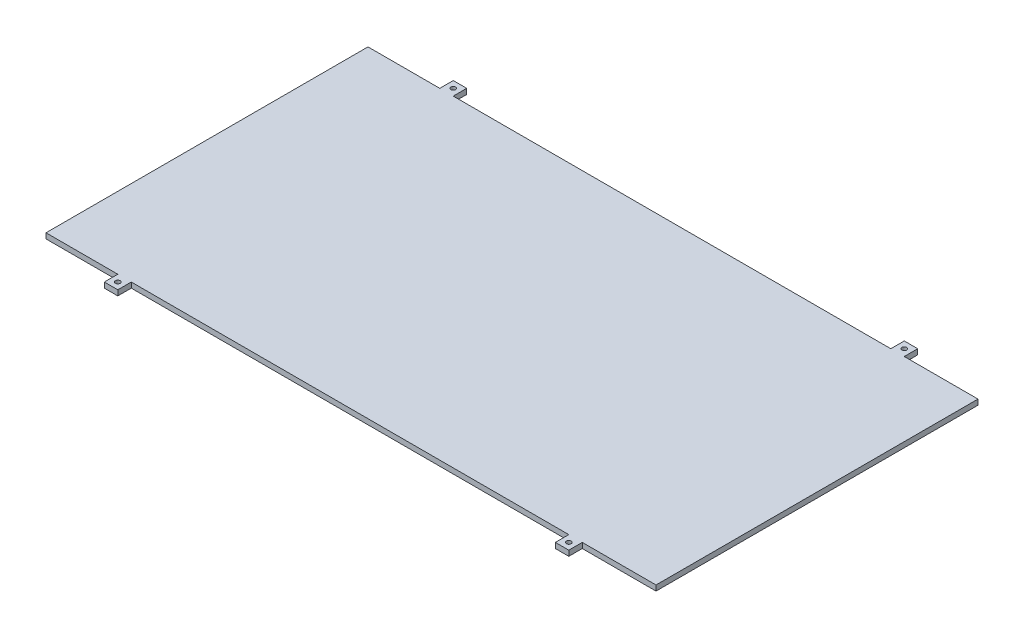
SolidWorks part; units mm, degrees
material "5052-H34"
ref_plane "Front Plane" through (0, 0, 0) normal (0, 0, 1) x (1, 0, 0)
ref_plane "Top Plane" through (0, 0, 0) normal (0, 1, 0) x (1, 0, 0)
ref_plane "Right Plane" through (0, 0, 0) normal (1, 0, 0) x (0, 0, -1)
sketch "Sketch1" plane through (0, 0, 0) normal (0, 0, 1) x (1, 0, 0)
  line L0 (-580.595, 4.4417) -> (-36.865, 4.4417)
  line L1 (-36.865, 4.4417) -> (-36.865, -0.3208)
  line L3 (-36.865, -0.3208) -> (-580.595, -0.3208)
  line L6 (-580.595, 4.4417) -> (-580.595, -0.3208)
  point P2 (-580.595, 4.4417)
extrude "Boss-Extrude1" add sketch "Sketch1" along normal blind 287
sketch "GasketGroove" plane through (0, -0.3208, 0) normal (0, -1, 0) x (1, 0, 0)
  line L0 (-577.595, 283) -> (-577.595, 4)
  line L1 (-576.595, 3) -> (-40.865, 3)
  line L2 (-39.865, 4) -> (-39.865, 283)
  line L3 (-40.865, 284) -> (-576.595, 284)
  line L4 (-579.595, 286) -> (-579.595, 1) construction
  line L5 (-577.595, 286) -> (-577.595, 1) construction
  line L6 (-37.865, 284) -> (-579.595, 284) construction
  line L7 (-579.595, 3) -> (-37.865, 3) construction
  line L8 (-39.865, 1) -> (-39.865, 286) construction
  line L9 (-579.595, 1) -> (-37.865, 1) construction
  line L10 (-37.865, 286) -> (-579.595, 286) construction
  line L11 (-37.865, 1) -> (-37.865, 286) construction
  line L14 (-37.865, 1) -> (-37.865, 286)
  line L15 (-579.595, 1) -> (-37.865, 1)
  line L16 (-579.595, 286) -> (-579.595, 1)
  line L17 (-37.865, 286) -> (-579.595, 286)
  line L18 (-37.865, 2) -> (-37.865, 285)
  line L19 (-578.595, 1) -> (-38.865, 1)
  line L20 (-579.595, 285) -> (-579.595, 2)
  line L21 (-38.865, 286) -> (-578.595, 286)
  arc A0 (-579.595, 2) -> (-578.595, 1) centre (-578.595, 2) ccw
  arc A1 (-579.595, 285) -> (-578.595, 286) centre (-578.595, 285) cw
  arc A2 (-37.865, 285) -> (-38.865, 286) centre (-38.865, 285) ccw
  arc A3 (-38.865, 1) -> (-37.865, 2) centre (-38.865, 2) ccw
  arc A4 (-40.865, 3) -> (-39.865, 4) centre (-40.865, 4) ccw
  arc A5 (-576.595, 3) -> (-577.595, 4) centre (-576.595, 4) cw
  arc A6 (-576.595, 284) -> (-577.595, 283) centre (-576.595, 283) ccw
  arc A7 (-39.865, 283) -> (-40.865, 284) centre (-40.865, 283) ccw
  dimension "D6" = 1
  dimension "D7" = 1
  dimension "D8" = 1
  dimension "D9" = 1
  dimension "D10" = 1
  dimension "D11" = 1
  dimension "D12" = 1
  dimension "D13" = 1
  dimension "D1" = 1
  dimension "D2" = 2
  dimension "D3" = 2
  dimension "D4" = 2
  dimension "D5" = 2
extrude "Cut-Extrude1" cut sketch "GasketGroove" against normal blind 1.3
sketch "Sketch2" plane through (0, 4.4417, 0) normal (0, 1, 0) x (1, 0, 0)
  line L0 (-516.595, 6) -> (-504.595, 6) construction
  line L1 (-516.595, -287) -> (-504.595, -287)
  line L2 (-516.595, -287) -> (-516.595, -299)
  line L3 (-516.595, -299) -> (-504.595, -299)
  line L4 (-36.865, 0) -> (-580.595, 0)
  line L5 (-580.595, 0) -> (-580.595, -287)
  line L6 (-580.595, -287) -> (-36.865, -287)
  line L7 (-36.865, -287) -> (-36.865, 0)
  line L9 (-580.595, 0) -> (-580.595, -287) construction
  line L11 (-36.865, -287) -> (-36.865, 0) construction
  line L12 (-504.595, -287) -> (-504.595, -299)
  line L13 (-114.595, -287) -> (-102.595, -287)
  line L14 (-114.595, -287) -> (-114.595, -299)
  line L15 (-114.595, -299) -> (-102.595, -299)
  line L16 (-102.595, -287) -> (-102.595, -299)
  line L17 (-516.595, 0) -> (-504.595, 0)
  line L18 (-516.595, 0) -> (-516.595, 12)
  line L19 (-516.595, 12) -> (-504.595, 12)
  line L20 (-504.595, 0) -> (-504.595, 12)
  line L21 (-114.595, 0) -> (-102.595, 0)
  line L22 (-114.595, 0) -> (-114.595, 12)
  line L23 (-114.595, 12) -> (-102.595, 12)
  line L24 (-102.595, 0) -> (-102.595, 12)
  line L25 (-114.595, 6) -> (-102.595, 6) construction
  line L26 (-114.595, -293) -> (-102.595, -293) construction
  line L27 (-516.595, -293) -> (-504.595, -293) construction
  circle A0 centre (-510.595, -293) radius 2.1
  circle A1 centre (-108.595, -293) radius 2.1
  circle A2 centre (-510.595, 6) radius 2.1
  circle A3 centre (-108.595, 6) radius 2.1
  dimension "D6" = 4.2
  dimension "D7" = 390
  dimension "D2" = 64
  dimension "D3" = 390
  dimension "D4" = 64
  dimension "D1" = 0
extrude "Boss-Extrude2" add sketch "Sketch2" against normal blind 4.7625
